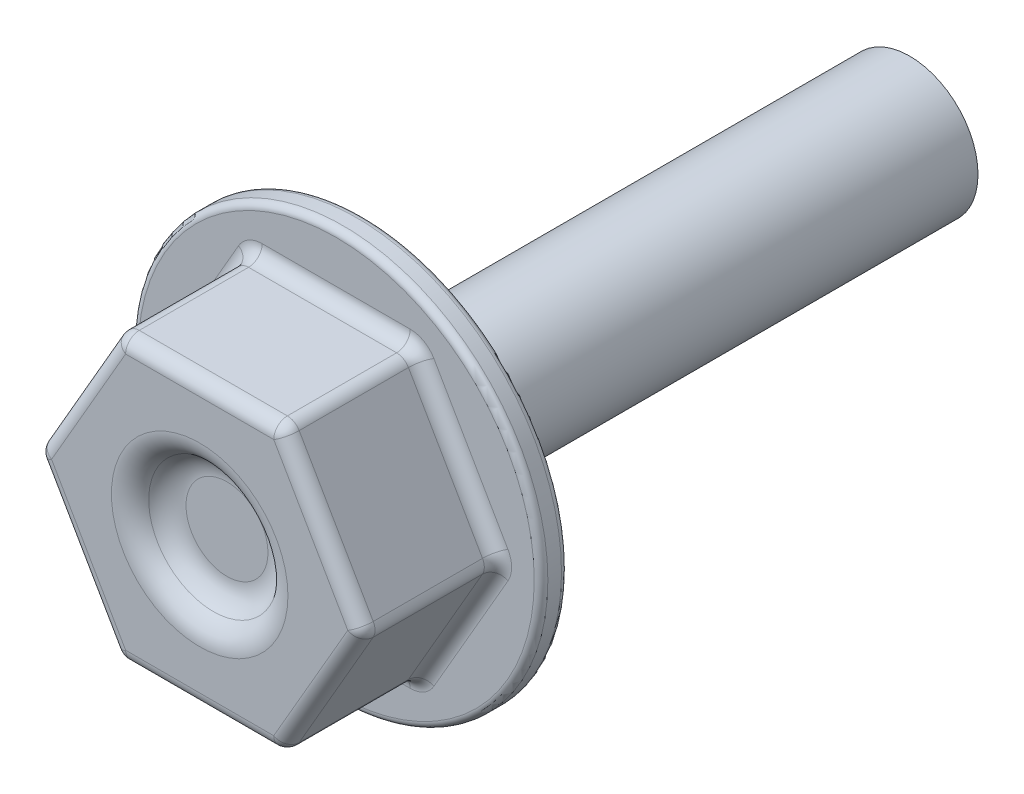
SolidWorks part; units mm, degrees
material "AISI 4140 Steel, quenched & tempered"
ref_plane "Front Plane" through (0, 0, 0) normal (1, 0, 0) x (0, 1, 0)
ref_plane "Top Plane" through (0, 0, 0) normal (0, 0, 1) x (0, 1, 0)
ref_plane "Right Plane" through (0, 0, 0) normal (0, 1, 0) x (-1, 0, 0)
sketch "Sketch1" plane through (0, 0, 0) normal (0, 0, 1) x (0, 1, 0)
  circle A0 centre (0, 0) radius 9
  circle A1 centre (0, 0) radius 15
  circle A2 centre (0, 0) radius 5
  dimension "D1" = 18
  dimension "D2" = 30
  dimension "D3" = 10
extrude "Boss-Extrude1" add sketch "Sketch1" against normal blind 40 contours A2
extrude "Boss-Extrude2" add sketch "Sketch1<3>" along normal blind 2 contours A1
sketch "Sketch1<3>" plane through (0, 0, 0) normal (0, 0, 1) x (0, 1, 0) same geometry as "Sketch1"
sketch "Sketch2" plane through (0, 0, 2) normal (0, 0, 1) x (1, 0, 0)
  line L1 (-12, 0) -> (-6, -10.3923)
  line L2 (-6, -10.3923) -> (6, -10.3923)
  line L3 (6, -10.3923) -> (12, 0)
  line L4 (12, 0) -> (6, 10.3923)
  line L5 (6, 10.3923) -> (-6, 10.3923)
  line L6 (-6, 10.3923) -> (-12, 0)
  circle A0 centre (0, 0) radius 10.3923 construction
  circle A1 centre (0, 0) radius 5
  dimension "D2" = 10
  dimension "D1" = 12
extrude "Boss-Extrude3" add sketch "Sketch2" along normal blind 10 contours L3 L4 L5 L6 L1 L2
extrude "Cut-Extrude1" cut sketch "Sketch2<3>" along normal up to surface (10 mm away) from offset 8 contours A1 up to face at (0, 0, 12)
sketch "Sketch2<3>" plane through (0, 0, 2) normal (0, 0, 1) x (1, 0, 0) same geometry as "Sketch2"
fillet "Fillet1" radius 0.5 2 edges at (15, 0, 0) (15, 0, 2)
fillet "Fillet2" radius 1 18 edges at (-6, -10.3923, 7) (-12, 0, 7) (-6, 10.3923, 7) (6, 10.3923, 7) (6, -10.3923, 7) (12, 0, 7) (-9, -5.1962, 12) (-9, 5.1962, 12) (0, 10.3923, 12) (9, -5.1962, 12) (0, -10.3923, 12) (9, 5.1962, 12) (9, -5.1962, 2) (0, 10.3923, 2) (-9, 5.1962, 2) (-9, -5.1962, 2) (0, -10.3923, 2) (9, 5.1962, 2)
fillet "Fillet3" radius 2 1 edges at (5, 0, 10)
fillet "Fillet4" radius 2 1 edges at (5, 0, 12)
scale "Scale1" scale about centroid uniform scaling yes scale factor 0.875
